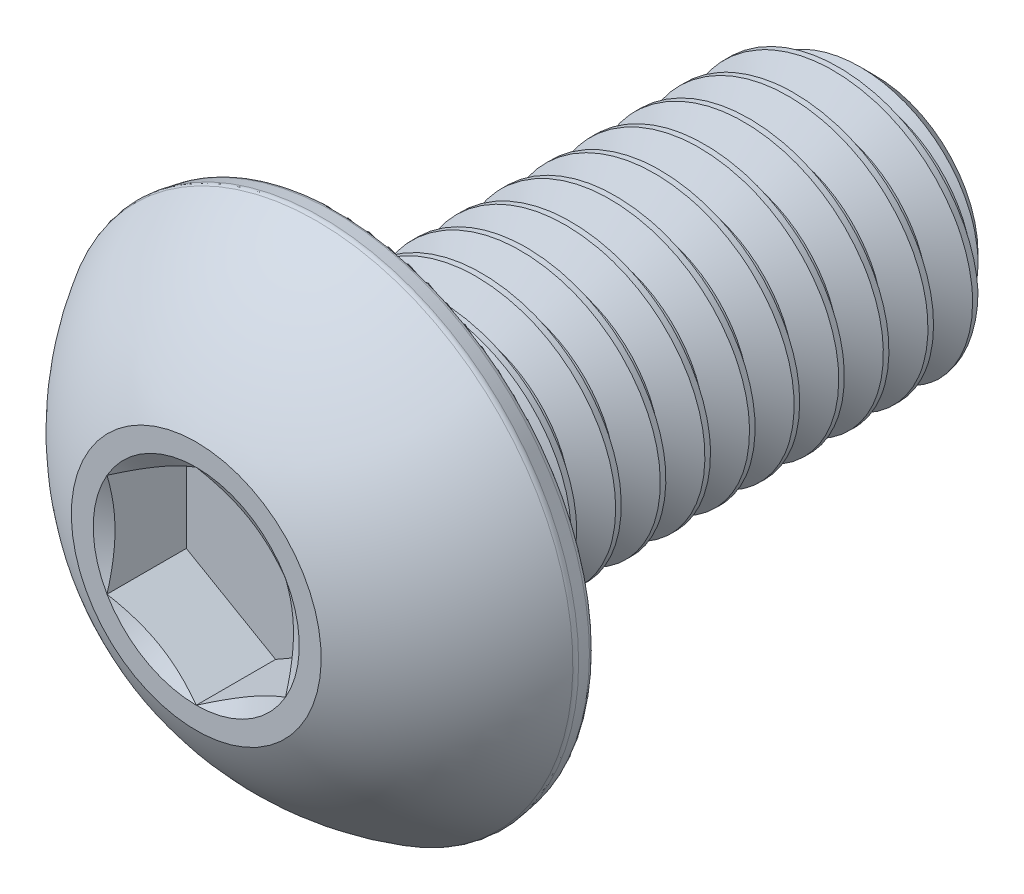
SolidWorks part; units mm, degrees
ref_plane "Front Plane" through (0, 0, 0) normal (0, 0, 1) x (1, 0, 0)
ref_plane "Top Plane" through (0, 0, 0) normal (0, 1, 0) x (1, 0, 0)
ref_plane "Right Plane" through (0, 0, 0) normal (1, 0, 0) x (0, 0, -1)
sketch "Sketch1" plane through (0, 0, 0) normal (1, 0, 0) x (0, 0, -1)
  line L0 (-6.0452, 0) -> (6.0452, 0) construction
  line L1 (-6.0452, 0) -> (-6.0452, 4.5847)
  line L2 (-6.0452, 4.5847) -> (-3.4798, 4.5847)
  line L3 (-3.4798, 4.5847) -> (-3.4798, 2.413)
  line L4 (-3.4798, 2.413) -> (6.0452, 2.413)
  line L5 (6.0452, 2.413) -> (6.0452, 0)
  point P2 (0, 0)
  point P4 (5.2514, 0)
  point P9 (4.8546, 2.413)
  point P10 (4.8546, -2.413)
  point P11 (6.0452, -2.413)
  point P15 (-4.6342, 0)
  dimension "Head Height" = 2.5654
  dimension "Head Diameter" = 9.1694
  dimension "Length" = 9.525
  dimension "Screw Size Decimal Equivalent" = 4.826
  dimension "Thread Pitch" = 0.7937
  dimension "D1" = 1.1906
  dimension "D2" = 1.411
sketch "Sketch2" plane through (0, 0, 0) normal (0, 0, 1) x (1, 0, 0)
  line L0 (0, 2.413) -> (0, 0) construction
  line L1 (0, 1.8331) -> (-1.5875, 0.9165)
  line L2 (-1.5875, 0.9165) -> (-1.5875, -0.9165)
  line L3 (-1.5875, -0.9165) -> (0, -1.8331)
  line L4 (0, -1.8331) -> (1.5875, -0.9165)
  line L5 (1.5875, -0.9165) -> (1.5875, 0.9165)
  line L6 (1.5875, 0.9165) -> (0, 1.8331)
  circle A0 centre (0, 0) radius 1.5875 construction
  circle A1 centre (0, 0) radius 2.2225
  point P10 (0, 2.2225)
  dimension "D1" = 4.445
  dimension "Drive Size" = 3.175
sketch "Sketch3" plane through (0, 0, 0) normal (1, 0, 0) x (0, 0, -1)
  line L0 (-6.0452, 0) -> (-6.0452, 2.2225)
  line L1 (-6.0452, 0) -> (-6.0452, 4.5847) construction
  line L2 (-6.0452, 4.5847) -> (-3.4798, 4.5847) construction
  line L3 (-3.8646, 4.5847) -> (-3.4798, 4.5168)
  line L4 (-3.4798, 4.5847) -> (-3.4798, 2.413) construction
  line L5 (-3.4798, 4.5168) -> (-3.4798, 2.413)
  line L6 (-6.0452, 0) -> (6.0452, 0) construction
  line L7 (-6.0452, 0) -> (6.0452, 0)
  line L8 (6.0452, 0) -> (6.0452, 1.8177)
  line L9 (6.0452, 2.413) -> (6.0452, 0) construction
  line L10 (6.0452, 1.8177) -> (5.4499, 2.413)
  line L11 (-3.4798, 2.413) -> (6.0452, 2.413) construction
  line L12 (5.4499, 2.413) -> (-3.4798, 2.413)
  arc A0 (-6.0452, 2.2225) -> (-3.8646, 4.5847) centre (-1.2678, 0) cw
  dimension "D1" = 0.3848
  dimension "D2" = 10
  dimension "D3" = 45
  dimension "D4" = 0.5953
revolve "Revolve1" add sketch "Sketch3" angle 360 about L7
sketch "Sketch4" plane through (0, 0, 6.0452) normal (0, 0, 1) x (1, 0, 0)
  line L0 (-1.5875, -0.9165) -> (0, -1.8331) construction
  line L1 (-1.5875, 0.9165) -> (-1.5875, -0.9165) construction
  line L2 (0, 1.8331) -> (-1.5875, 0.9165) construction
  line L3 (1.5875, 0.9165) -> (0, 1.8331) construction
  line L4 (1.5875, -0.9165) -> (1.5875, 0.9165) construction
  line L5 (0, -1.8331) -> (1.5875, -0.9165) construction
  line L6 (-1.5875, -0.9165) -> (0, -1.8331)
  line L7 (-1.5875, 0.9165) -> (-1.5875, -0.9165)
  line L8 (0, 1.8331) -> (-1.5875, 0.9165)
  line L9 (1.5875, 0.9165) -> (0, 1.8331)
  line L10 (1.5875, -0.9165) -> (1.5875, 0.9165)
  line L11 (0, -1.8331) -> (1.5875, -0.9165)
extrude "Cut-Extrude1" cut sketch "Sketch4" against normal up to vertex (1.411 mm away) up to point (0, 0, 4.6342)
sketch "Sketch5" plane through (0, 0, 6.0452) normal (0, 0, 1) x (1, 0, 0)
  circle A0 centre (0, 0) radius 1.8331
extrude "Cut-Extrude2" cut sketch "Sketch5" against normal up to vertex (1.411 mm away) draft 60 up to point (0, 0, 4.6342)
fillet "Fillet1" radius 0.1283 2 edges at (4.5847, 0, 3.8646) (4.5168, 0, 3.4798)
split "Split1" bodies to split 106 resulting bodies 107 108 split by face at (4.4092, 0, 3.4798)
sketch "Sketch6" plane through (0, 0, -6.0452) normal (0, 0, -1) x (-1, 0, 0)
  circle A0 centre (0, 0) radius 2.413 construction
  circle A1 centre (0, 0) radius 2.413
curve "Helix/Spiral1" pitch 0.7937 height 10.3187 radius 2.413 centre (0, 0, -6.0452) axis (0, 0, 1) start towards (0, 1, 0)
sketch "Sketch7" plane through (0, 0, 0) normal (1, 0, 0) x (0, 0, -1)
  line L0 (5.9956, 2.4989) -> (6.3925, 1.8115) construction
  line L1 (6.3925, 1.8115) -> (6.7893, 2.4989) construction
  line L2 (6.7893, 2.4989) -> (5.9956, 2.4989) construction
  line L3 (6.0204, 2.456) -> (6.7645, 2.456)
  line L4 (6.7645, 2.456) -> (6.4421, 1.8974)
  line L5 (6.4421, 1.8974) -> (6.3429, 1.8974)
  line L6 (6.3429, 1.8974) -> (6.0204, 2.456)
  line L7 (6.3925, 1.8974) -> (6.3925, 1.8115) construction
  line L8 (6.0452, 2.413) -> (6.7397, 2.413) construction
  line L9 (6.3925, 2.4989) -> (6.3925, 2.413) construction
  point P12 (6.3925, 2.456)
  dimension "D1" = 0.7937
  dimension "D2" = 0.0992
sweep "Cut-Sweep1" cut profiles "Sketch7" path "Helix/Spiral1" align with end faces yes
sketch "Sketch8" plane through (0, 0, 3.4798) normal (0, 0, -1) x (-1, 0, 0)
  circle A0 centre (0, 0) radius 2.4989
extrude "Boss-Extrude1" add sketch "Sketch8" along normal up to vertex (8.3344 mm away) draft 45 up to point (0, 2.413, -4.8546)
equation "\"D1@Sketch1\"=\"Thread Pitch@Sketch1\"*1.5"
equation "\"D2@Sketch1\"=0.55*\"Head Height@Sketch1\""
equation "\"D1@Sketch2\"=\"Drive Size@Sketch2\"*1.4"
equation "\"D1@Sketch3\"=0.15*\"Head Height@Sketch1\""
equation "\"D4@Sketch3\"=0.75*\"Thread Pitch@Sketch1\""
equation "\"D1@Fillet1\"=.05*\"Head Height@Sketch1\""
equation "\"D4@Helix/Spiral1\"=\"Thread Pitch@Sketch1\""
equation "\"D3@Helix/Spiral1\"=\"Length@Sketch1\"+\"Thread Pitch@Sketch1\""
equation "\"D2@Sketch7\"=\"D1@Sketch7\"/8"
equation "\"D1@Sketch7\"=\"Thread Pitch@Sketch1\""
